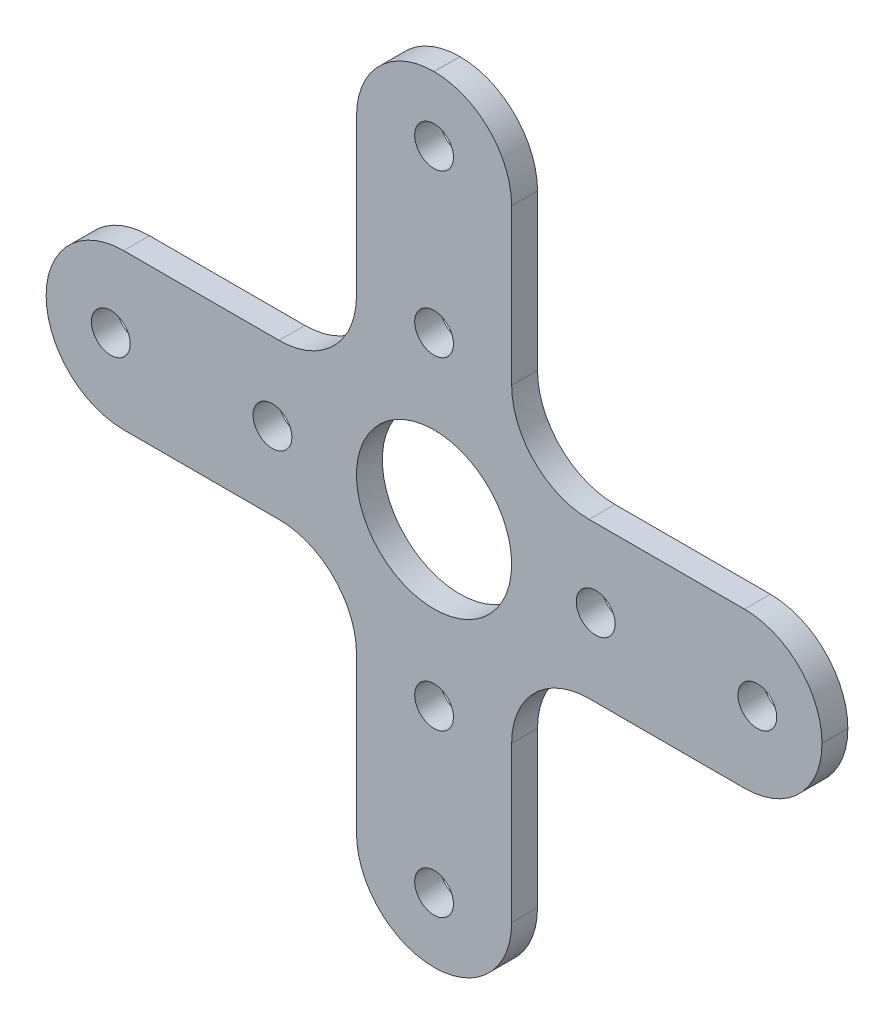
SolidWorks part; units mm, degrees
material "ABS"
ref_plane "Front Plane" through (0, 0, 0) normal (0, 0, 1) x (1, 0, 0)
ref_plane "Top Plane" through (0, 0, 0) normal (0, 1, 0) x (1, 0, 0)
ref_plane "Right Plane" through (0, 0, 0) normal (1, 0, 0) x (0, 0, -1)
sketch "Sketch1" plane through (0, 0, 0) normal (0, 0, 1) x (1, 0, 0)
  line L0 (11.99, -6) -> (24.01, -6)
  line L1 (-24.01, -6) -> (-11.99, -6)
  line L2 (-30, -0.01) -> (-30, 0.01)
  line L3 (-24.01, 6) -> (-11.99, 6)
  line L4 (30, -0.01) -> (30, 0.01)
  line L5 (-30, -6) -> (30, 6) construction
  line L6 (-30, 6) -> (30, -6) construction
  line L7 (-0.01, -30) -> (0.01, -30)
  line L8 (-6, -24.01) -> (-6, -11.99)
  line L9 (-0.01, 30) -> (0.01, 30)
  line L10 (6, -24.01) -> (6, -11.99)
  line L11 (-6, -30) -> (6, 30) construction
  line L12 (-6, 30) -> (6, -30) construction
  line L13 (-6, 11.99) -> (-6, 24.01)
  line L14 (11.99, 6) -> (24.01, 6)
  line L15 (6, 11.99) -> (6, 24.01)
  line L16 (55, 0) -> (-55, 0) construction
  line L17 (0, -55) -> (0, 55) construction
  circle A0 centre (0, 0) radius 6
  circle A1 centre (-25, 0) radius 1.5
  circle A2 centre (25, 0) radius 1.5
  circle A3 centre (0, 25) radius 1.5
  circle A4 centre (0, -25) radius 1.5
  arc A5 (-0.01, 30) -> (-6, 24.01) centre (-0.01, 24.01) ccw
  arc A6 (0.01, 30) -> (6, 24.01) centre (0.01, 24.01) cw
  arc A7 (6, -11.99) -> (11.99, -6) centre (11.99, -11.99) cw
  arc A8 (-6, -11.99) -> (-11.99, -6) centre (-11.99, -11.99) ccw
  arc A9 (-11.99, 6) -> (-6, 11.99) centre (-11.99, 11.99) ccw
  arc A10 (11.99, 6) -> (6, 11.99) centre (11.99, 11.99) cw
  arc A11 (24.01, -6) -> (30, -0.01) centre (24.01, -0.01) ccw
  arc A12 (30, 0.01) -> (24.01, 6) centre (24.01, 0.01) ccw
  arc A13 (0.01, -30) -> (6, -24.01) centre (0.01, -24.01) ccw
  arc A14 (-0.01, -30) -> (-6, -24.01) centre (-0.01, -24.01) cw
  arc A15 (-24.01, -6) -> (-30, -0.01) centre (-24.01, -0.01) cw
  arc A16 (-30, 0.01) -> (-24.01, 6) centre (-24.01, 0.01) cw
  circle A17 centre (0, 12.5) radius 1.5
  circle A18 centre (0, -12.5) radius 1.5
  circle A19 centre (-12.5, 0) radius 1.5
  circle A20 centre (12.5, 0) radius 1.5
  point P0 (0, 0)
  point P6 (0, 0)
  point P37 (6, -6)
  point P42 (-6, 6)
  point P45 (6, 6)
  dimension "D5" = 12
  dimension "D6" = 3
  dimension "D8" = 3
  dimension "D10" = 5.99
  dimension "D11" = 5.99
  dimension "D12" = 5.99
  dimension "D14" = 3
  dimension "D16" = 3
  dimension "D1" = 60
  dimension "D2" = 60
  dimension "D3" = 12
  dimension "D4" = 12
  dimension "D7" = 25
  dimension "D9" = 25
  dimension "D13" = 12.5
  dimension "D15" = 12.5
extrude "Boss-Extrude1" add sketch "Sketch1" along normal blind 2
